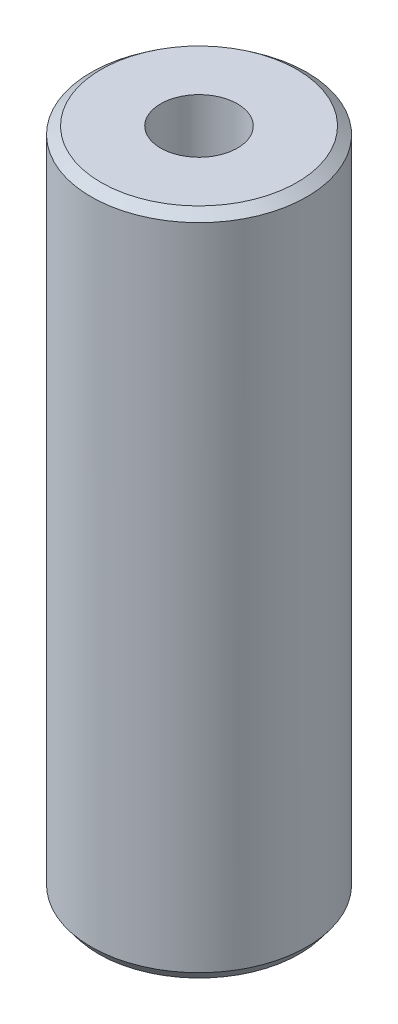
SolidWorks part; units mm, degrees
ref_plane "Front Plane" through (0, 0, 0) normal (0, 0, 1) x (1, 0, 0)
ref_plane "Top Plane" through (0, 0, 0) normal (0, 1, 0) x (1, 0, 0)
ref_plane "Right Plane" through (0, 0, 0) normal (1, 0, 0) x (0, 0, -1)
sketch "Sketch1" plane through (0, 0, 0) normal (0, 1, 0) x (1, 0, 0)
  circle A0 centre (0, 0) radius 20
  dimension "SHAFT_OD" = 40
extrude "Boss-Extrude1" add sketch "Sketch1" along normal blind 123.6578
sketch "Sketch2" plane through (0, 0, 0) normal (0, 1, 0) x (1, 0, 0)
  circle A0 centre (0, 0) radius 7.1211
  dimension "BORE_D" = 14.2421
extrude "Cut-Extrude1" cut sketch "Sketch2" along normal through all
chamfer "Chamfer1" distance 1.3886 angle 52.934 2 edges at (0, 123.6578, 20) (0, 0, 20) first distance on face at (0, 123.6578, 20) first distance on face at (0, 0, 7.1211)
